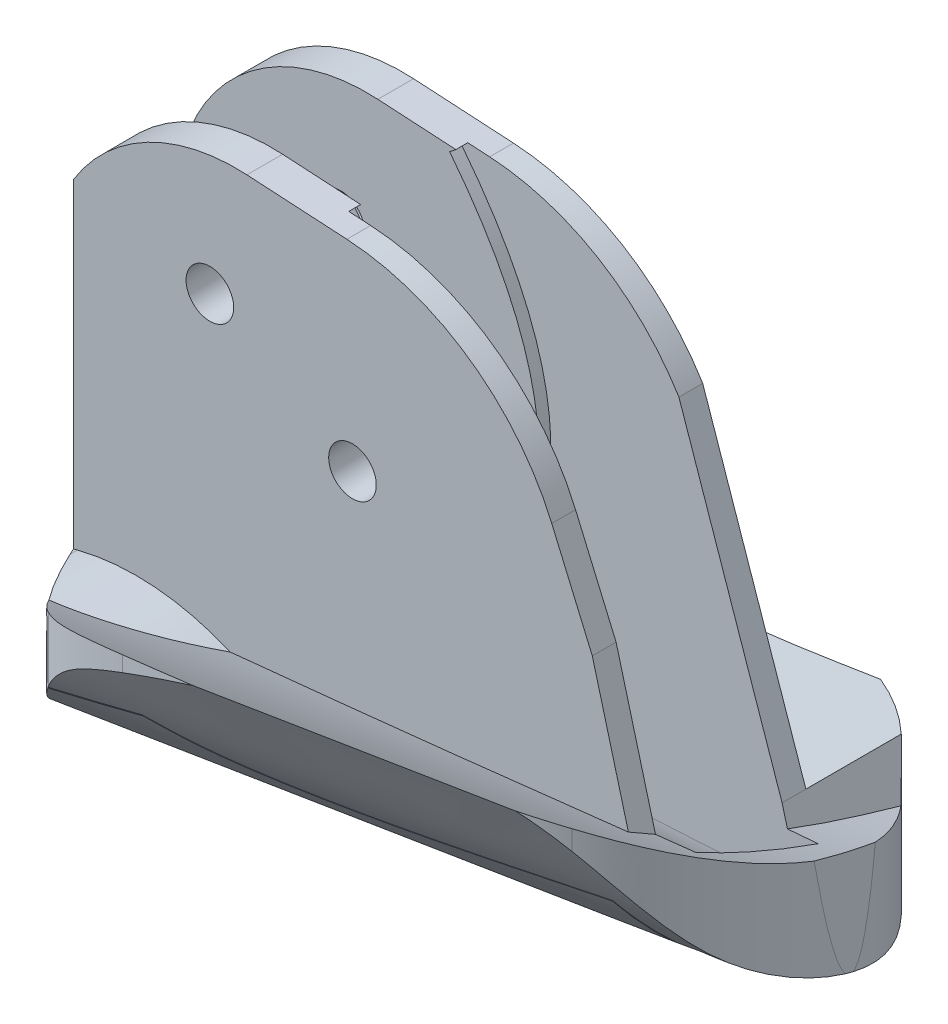
SolidWorks part; units mm, degrees
ref_plane "Спереди" through (0, 0, 0) normal (0, 0, 1) x (1, 0, 0)
ref_plane "Сверху" through (0, 0, 0) normal (0, 1, 0) x (1, 0, 0)
ref_plane "Справа" through (0, 0, 0) normal (1, 0, 0) x (0, 0, -1)
sketch "Sketch5" plane through (0, 0, 0) normal (0, 0, 1) x (1, 0, 0)
  line L0 (1.7523, 0.4742) -> (37.3029, 86.8114) construction
  line L1 (-1.0106, -0.6044) -> (29.6618, 87.5839) construction
  line L2 (0, 0) -> (17.8901, 43.1295)
  line L3 (0, 0) -> (114.3643, 0) construction
  line L4 (23.8823, 39.6684) -> (24.5035, 51.2503)
  line B0 (17.4507, 115.16) -> (29.9551, 112.6983)
  spline B1 degree 3 poles (29.9551, 112.6983) (28.321, 116.0983) (27.9284, 121.1676) (30.1713, 134.4746) (29.8473, 132.0116) (30.6222, 139.9349) (27.0176, 140.9027) knots 0 0 0 0 0.297085 0.369784 0.687298 1 1 1 1
  spline B2 degree 2 poles (27.0176, 140.9027) (20.5603, 128.6427) (17.4507, 115.16) knots 0 0 0 1 1 1
  spline B3 degree 2 poles (27.0176, 140.9027) (26.5004, 134.6878) (22.2537, 130.5645) knots 0 0 0 1 1 1
  line B4 (17.1977, 114.3508) -> (29.842, 112.2111)
  line B5 (28.7001, 84.8969) -> (10.3668, 87.513)
  spline B6 degree 1 poles (17.1977, 114.3508) (10.3668, 87.513) knots 0 0 1 1
  spline B7 degree 2 poles (29.842, 112.2111) (22.5534, 98.8452) (28.7001, 84.8969) knots 0 0 0 1 1 1
  line B8 (10.1904, 87.4159) -> (28.2572, 84.4958)
  line B9 (32.8909, 45.7292) -> (10.0695, 42.8593)
  spline B10 degree 2 poles (10.1904, 87.4159) (10.0234, 65.1379) (10.0695, 42.8593) knots 0 0 0 1 1 1
  spline B11 degree 2 poles (28.2572, 84.4958) (20.6417, 64.1094) (32.8909, 45.7292) knots 0 0 0 1 1 1
  line B12 (10.2797, 36.8758) -> (3.9253, -13.9853)
  line B13 (3.9253, -13.9853) -> (33.9594, -31.0804)
  line B14 (33.9594, -31.0804) -> (45.9193, -27.7969)
  line B15 (45.9193, -27.7969) -> (58.2918, -13.9853)
  line B16 (58.2918, -13.9853) -> (69.0331, -4.9875)
  line B17 (69.0331, -4.9875) -> (82.514, 2.0236)
  line B18 (82.514, 2.0236) -> (89.2736, 3.8794)
  line B19 (89.2736, 3.8794) -> (92.4846, 9.5208)
  line B20 (92.4846, 9.5208) -> (96.8914, 17.263)
  line B21 (96.8914, 17.263) -> (101.4978, 21.1217)
  line B22 (101.4978, 21.1217) -> (103.9241, 23.1541)
  line B23 (104.261, 27.4157) -> (104.5375, 25.5318)
  line B24 (84.192, 21.2056) -> (87.7484, 22.7822)
  line B25 (87.7484, 22.7822) -> (92.912, 27.4956)
  line B26 (71.6086, 15.6268) -> (84.192, 21.2056)
  line B27 (92.912, 27.4956) -> (95.357, 29.7274)
  line B28 (95.357, 29.7274) -> (96.8049, 29.9399)
  line B29 (71.6086, 15.6268) -> (53.4239, 15.2713)
  line B30 (48.0904, 17.5622) -> (39.9394, 26.4919)
  line B31 (39.9394, 26.4919) -> (33.9594, 37.99)
  line B32 (33.9594, 37.99) -> (10.2797, 36.8758)
  line B33 (96.8049, 29.9399) -> (99.4078, 30.2175)
  line B34 (99.4078, 30.2175) -> (102.2786, 29.261)
  line B35 (102.2786, 29.261) -> (104.261, 27.4157)
  line B36 (104.5375, 25.5318) -> (103.9241, 23.1541)
  arc B37 (53.4239, 15.2713) -> (48.0904, 17.5622) centre (53.2864, 22.3051) cw
  spline B38 degree 3 poles (104.261, 27.4157) (103.5289, 27.0494) (99.8378, 26.2685) (94.8982, 17.2338) (98.6516, 18.7375) knots 0 0 0 0 0.441207 1 1 1 1
  line B39 (27.7375, 116.5129) -> (14.1959, 87.8955)
  line B40 (27.7375, 116.5129) -> (25.9485, 114.8372)
  line B41 (25.9485, 114.8372) -> (27.5763, 114.067)
  line B42 (27.7375, 116.5129) -> (27.5763, 114.067)
  line B43 (26.1527, 88.0864) -> (17.8901, 43.1295)
  line B44 (19.3622, 85.005) -> (23.8823, 39.6684)
  line B45 (19.3622, 85.005) -> (17.7584, 73.9508)
  line B46 (17.7584, 73.9508) -> (23.117, 74.485)
  line B47 (23.117, 74.485) -> (19.3622, 85.005)
  line B48 (26.1527, 88.0864) -> (23.7481, 82.7635)
  line B49 (23.7481, 82.7635) -> (25.1278, 82.5099)
  line B50 (25.1278, 82.5099) -> (26.5087, 82.2561)
  line B51 (26.5087, 82.2561) -> (26.1527, 88.0864)
  line B52 (26.1527, 88.0864) -> (19.3622, 85.005)
  line B53 (19.3622, 85.005) -> (22.3683, 87.7853)
  line B54 (22.3683, 87.7853) -> (22.9012, 86.6109)
  line B55 (22.9012, 86.6109) -> (23.4998, 85.2917)
  line B56 (23.4998, 85.2917) -> (19.3622, 85.005)
  dimension "D1" = 93.37
  dimension "D2" = 93.37
  dimension "D4" = 67.471
  dimension "D5" = 8.764
sketch_block_instance "Block1-1"
sketch_block "Block1"
sketch_block_instance "Block2-1"
sketch_block "Block2"
sketch_block_instance "Block3-1"
sketch_block "Block3"
sketch_block_instance "Block18-1"
sketch_block "Block18"
sketch_block_instance "Block44-1"
sketch_block "Block44"
sketch_block_instance "Block46-1"
sketch_block "Block46"
sketch_block_instance "Block47-1"
sketch_block "Block47"
sketch_block_instance "Block48-1"
sketch_block "Block48"
sketch_block_instance "Block50-1"
sketch_block "Block50"
sketch "Sketch10" plane through (0, 0, 0) normal (0, 0, 1) x (1, 0, 0)
  line L0 (29.8177, 47.6353) -> (33.9594, 37.99)
  line L1 (23.8823, 39.6684) -> (24.3862, 39.4642) construction
  line L2 (23.8823, 39.6684) -> (24.2846, 40.0707) construction
  line L3 (33.9594, 37.99) -> (36.9938, 26.6828)
  line L21 (10.2797, 36.8758) -> (12.7888, 23.6588)
  line L22 (12.7888, 23.6588) -> (36.9938, 26.6828)
  line L23 (10.2797, 36.8758) -> (12.3212, 48.6513)
  line L24 (12.3212, 48.6513) -> (29.8177, 47.6353)
  circle A0 centre (17.8901, 43.1295) radius 1
  circle A1 centre (23.8823, 39.6684) radius 1
  dimension "D1" = 2
  dimension "D2" = 2
extrude "Boss-Extrude5" add sketch "Sketch10" along normal mid plane 15
sketch "Sketch11" plane through (0, 0, 7.5) normal (0, 0, 1) x (1, 0, 0)
  line L0 (17.8254, 32.4239) -> (9.1237, 30.2079)
  line L1 (37.7529, 30.846) -> (34.6935, 60.2717)
  line L2 (34.6935, 60.2717) -> (6.5943, 53.1599)
  line L3 (6.5943, 53.1599) -> (9.1237, 30.2079)
  line L4 (37.7529, 30.846) -> (30.6791, 30.1551) construction
  line L5 (30.6791, 30.1551) -> (19.269, 26.7342) construction
  line L6 (19.269, 26.7342) -> (17.8254, 32.4239) construction
  line L7 (12.3212, 48.6513) -> (10.2797, 36.8758) construction
  spline S1 degree 3 poles (37.7529, 30.846) (30.6791, 30.1551) (19.269, 26.7342) (17.8254, 32.4239) knots 0 0 0 0 1 1 1 1
extrude "Cut-Extrude1" cut sketch "Sketch11" against normal blind 4
fillet "Fillet1" radius 10 1 edges at (29.8177, 47.6353, -2)
extrude "Cut-Extrude6" cut sketch "Sketch11<2>" against normal blind 10 from offset 11 offset against normal yes
sketch "Sketch11<2>" plane through (0, 0, 7.5) normal (0, 0, 1) x (1, 0, 0) same geometry as "Sketch11"
sketch "Sketch16" plane through (0, 0, 0) normal (0, 0, 1) x (1, 0, 0)
  line L1 (10.0743, 54.3608) -> (34.4186, 54.3608)
  line L2 (10.0743, 54.3608) -> (10.0743, 40.6451)
  line L3 (10.0743, 40.6451) -> (34.4186, 36.6644)
  line L4 (34.4186, 54.3608) -> (34.4186, 36.6644)
extrude "Cut-Extrude7" cut sketch "Sketch16" against normal mid plane 4
sketch "Sketch26" plane through (41.1882, 11.0532, 0) normal (0.9658, 0.2592, 0) x (0, 0, -1)
  line L12 (2, 27.8898) -> (2, 26.5356)
  line L13 (2, 26.5356) -> (-2, 26.5356)
  line L14 (-2, 26.5356) -> (-2, 27.8898)
  line L15 (-2, 27.8898) -> (-3.5, 27.8898)
  line L16 (-3.5, 27.8898) -> (-3.5, 20.2671)
  line L17 (-3.5, 20.2671) -> (-7.5, 20.2671)
  line L18 (-7.5, 20.2671) -> (-7.5, 16.1826)
  line L19 (-7.5, 16.1826) -> (7.5, 16.1826)
  line L20 (7.5, 16.1826) -> (7.5, 20.2671)
  line L21 (7.5, 20.2671) -> (3.5, 20.2671)
  line L22 (3.5, 20.2671) -> (3.5, 27.8898)
  line L23 (3.5, 27.8898) -> (2, 27.8898)
  line L24 (2, 27.8898) -> (2, 26.5356)
  line L25 (2, 26.5356) -> (-2, 26.5356)
  line L26 (-2, 26.5356) -> (-2, 27.8898)
  line L27 (-2, 27.8898) -> (-3.5, 27.8898)
  line L28 (-3.5, 27.8898) -> (-3.5, 20.2671)
  line L29 (-3.5, 20.2671) -> (-7.5, 20.2671)
  line L30 (-7.5, 20.2671) -> (-7.5, 16.1826)
  line L31 (-7.5, 16.1826) -> (7.5, 16.1826)
  line L32 (7.5, 16.1826) -> (7.5, 20.2671)
  line L33 (7.5, 20.2671) -> (3.5, 20.2671)
  line L34 (3.5, 20.2671) -> (3.5, 27.8898)
  line L35 (3.5, 27.8898) -> (2, 27.8898)
  dimension "D1" = 0
extrude "Boss-Extrude11" add sketch "Sketch26" along normal blind 9
sketch "Sketch28" plane through (-4.1944, 15.6296, 0) normal (0.2592, -0.9658, 0) x (0.9658, 0.2592, 0)
  line L0 (38.2441, 4.6151) -> (38.2441, -4.6151) construction
  line L1 (51.6455, 0) -> (42.6455, 0) construction
  line L2 (51.6455, 7.5) -> (51.6455, -7.5) construction
  line L3 (42.6455, 7.5) -> (42.6455, -7.5) construction
  circle A0 centre (38.2441, 4.6151) radius 1
  circle A1 centre (38.2441, -4.6151) radius 1
  point P10 (38.2441, 0)
  dimension "D1" = 2
sketch "Sketch32" plane through (49.8806, 13.3859, 0) normal (0.9658, 0.2592, 0) x (0, 0, -1)
  line L12 (3.5, 27.8898) -> (2, 27.8898)
  line L13 (2, 27.8898) -> (2, 26.5356)
  line L14 (2, 26.5356) -> (-2, 26.5356)
  line L15 (-2, 26.5356) -> (-2, 27.8898)
  line L16 (-2, 27.8898) -> (-3.5, 27.8898)
  line L17 (-3.5, 27.8898) -> (-3.5, 20.2671)
  line L18 (-3.5, 20.2671) -> (-7.5, 20.2671)
  line L19 (-7.5, 20.2671) -> (-7.5, 16.1826)
  line L20 (-7.5, 16.1826) -> (7.5, 16.1826)
  line L21 (7.5, 16.1826) -> (7.5, 20.2671)
  line L22 (7.5, 20.2671) -> (3.5, 20.2671)
  line L23 (3.5, 20.2671) -> (3.5, 27.8898)
  line L24 (3.5, 27.8898) -> (2, 27.8898)
  line L25 (2, 27.8898) -> (2, 26.5356)
  line L26 (2, 26.5356) -> (-2, 26.5356)
  line L27 (-2, 26.5356) -> (-2, 27.8898)
  line L28 (-2, 27.8898) -> (-3.5, 27.8898)
  line L29 (-3.5, 27.8898) -> (-3.5, 20.2671)
  line L30 (-3.5, 20.2671) -> (-7.5, 20.2671)
  line L31 (-7.5, 20.2671) -> (-7.5, 16.1826)
  line L32 (-7.5, 16.1826) -> (7.5, 16.1826)
  line L33 (7.5, 16.1826) -> (7.5, 20.2671)
  line L34 (7.5, 20.2671) -> (3.5, 20.2671)
  line L35 (3.5, 20.2671) -> (3.5, 27.8898)
  dimension "D1" = 0
extrude "Cut-Extrude9" cut sketch "Sketch32" against normal blind 9
fillet "Fillet2" radius 8 2 edges at (12.3212, 48.6513, 2.75) (12.3212, 48.6513, -2.75)
fillet "Fillet3" radius 10 2 edges at (17.8254, 32.4239, 5.5) (17.8254, 32.4239, -5.5)
sketch "Sketch33" plane through (0, 0, -7.5) normal (0, 0, -1) x (-1, 0, 0)
  line L8 (-11.4338, 30.7962) -> (-12.3264, 31.0236)
  line L9 (-35.9352, 30.6278) -> (-36.9938, 26.6828)
  line L10 (-36.9938, 26.6828) -> (-12.7888, 23.6588)
  line L15 (-12.7888, 23.6588) -> (-11.4338, 30.7962)
  line L16 (-11.4338, 30.7962) -> (-12.3264, 31.0236)
  line L17 (-35.9352, 30.6278) -> (-36.9938, 26.6828)
  line L18 (-36.9938, 26.6828) -> (-12.7888, 23.6588)
  line L23 (-12.7888, 23.6588) -> (-11.4338, 30.7962)
  arc A1 (-12.3264, 31.0236) -> (-19.6523, 30.0735) centre (-14.7943, 21.3329) ccw
  arc A2 (-12.3264, 31.0236) -> (-19.6523, 30.0735) centre (-14.7943, 21.3329) ccw
  spline S1 degree 3 poles (-2248.4451, 2036.9138) (2398.2149, -1976.4492) (-2488.6024, 2006.9679) (2269.0143, -1889.1309) knots -4.784802 -4.784802 -4.784802 -4.784802 6.242241 6.242241 6.242241 6.242241 only from (-19.6523, 30.0735) to (-35.9352, 30.6278)
  spline S2 degree 3 poles (-19.6523, 30.0735) (-23.0941, 28.1606) (-30.3498, 29.8586) (-35.9352, 30.6278) knots 0.191602 0.191602 0.191602 0.191602 0.918086 0.918086 0.918086 0.918086
  line M11 (-11.4338, 30.7962) -> (-12.3264, 31.0236)
  arc M12 (-12.3264, 31.0236) -> (-19.6523, 30.0735) centre (-14.7943, 21.3329) ccw
  spline M13 degree 3 poles (-37.7529, 30.846) (-30.6791, 30.1551) (-19.269, 26.7342) (-17.8254, 32.4239) knots 0 0 0 0 1 1 1 1 only from (-19.6523, 30.0735) to (-35.9352, 30.6278)
  line M14 (-35.9352, 30.6278) -> (-36.9938, 26.6828)
  line M15 (-36.9938, 26.6828) -> (-12.7888, 23.6588)
  line M19 (-36.9938, 26.6828) -> (-12.7888, 23.6588)
  line M20 (-12.7888, 23.6588) -> (-11.4338, 30.7962)
  dimension "D1" = 0
extrude "Boss-Extrude15" add sketch "Sketch33" along normal blind 2 contours M20 M11 M12 M13 M14 M15 M19 region at (22.5887, 27.6255, -7.5)
ref_plane "Plane1" through (38.4615, 25.5911, -2.6463) normal (-0.987, -0.0285, 0.1584) x (0.1583, 0.0046, 0.9874)
sketch "Sketch34" plane through (38.4615, 25.5911, -2.6463) normal (-0.987, -0.0285, 0.1584) x (0.1583, 0.0046, 0.9874)
  line L1 (-9.9613, -0.7387) -> (-10.5398, -8.5297)
  line L3 (-10.5398, -8.5297) -> (14.0671, -4.6342)
  line L4 (14.0671, -4.6342) -> (11.4688, 6.9569)
  line L5 (11.4688, 6.9569) -> (11.2103, 7.3048)
  line L6 (9.3619, 9.0979) -> (11.2103, 7.3048)
  spline S1 degree 3 poles (9.3619, 9.0979) (8.0808, 7.1287) (6.1822, 3.4329) (1.2126, 0.2397) (-4.0234, -1.2627) (-7.9896, -1.4142) (-9.9613, -0.7387) knots 0 0 0 0 0.305307 0.51081 0.734727 1 1 1 1
extrude "Cut-Extrude10" cut sketch "Sketch34" along normal blind 39
sketch "Sketch35" plane through (38.4615, 25.5911, -2.6463) normal (-0.987, -0.0285, 0.1584) x (0.1583, 0.0046, 0.9874)
  line L0 (9.4005, 9.1848) -> (3.3279, 5.0721) construction
  line L1 (3.3279, 5.0721) -> (-2.7348, 1.7749) construction
  line L2 (-2.7348, 1.7749) -> (-13.1414, 3.4012) construction
  line L5 (-13.1414, 3.4012) -> (-9.5787, -0.8831) construction
  spline S0 degree 3 poles (9.4005, 9.1848) (8.0149, 7.019) (5.8425, 2.8785) (-1.139, -0.8866) (-6.3054, -1.5967) (-9.5787, -0.8831) knots 0 0 0 0 0.341444 0.573298 1 1 1 1
  spline S1 degree 3 poles (6.8156, 5.1075) (6.3414, 4.4434) (5.0935, 2.8969) (3.4618, 1.7144) (2.4324, 1.1336) knots 0.201432 0.201432 0.201432 0.201432 0.305307 0.455135 0.455135 0.455135 0.455135 construction
  spline S2 degree 3 poles (-5.3799, -1.1913) (-4.8408, -1.1453) (-2.5388, -0.8367) (0.0833, -0.0843) (2.0499, 0.9178) (2.4324, 1.1336) knots 0.196975 0.196975 0.196975 0.196975 0.265273 0.48919 0.544865 0.544865 0.544865 0.544865 construction
  spline S3 degree 4 poles (9.4005, 9.1848) (3.3279, 5.0721) (-2.7348, 1.7749) (-13.1414, 3.4012) (-9.5787, -0.8831) knots 0 0 0 0 0 1 1 1 1 1
extrude "Boss-Extrude16" add sketch "Sketch35" along normal blind 35
sketch "Sketch36" plane through (0, 0, 0) normal (0, 1, 0) x (1, 0, 0)
  line L0 (22.2747, 9.702) -> (19.2802, 8.5421)
  circle A0 centre (26.2258, -0.6503) radius 26.4347
  arc A1 (32.0453, -8.6033) -> (26.2258, -9.3573) centre (2192.8185, -16707.6767) ccw
  spline S27 degree 3 poles (27.8922, 10.6475) (26.9334, 10.6337) (25.9886, 10.5289) (24.5845, 10.2862) (24.1189, 10.1901) (23.1921, 9.9682) (22.73, 9.842) (22.2747, 9.702) knots 0 0 0 0 0.5 0.5 0.75 0.75 1 1 1 1
  spline S29 degree 3 poles (19.2802, 8.5421) (18.1759, 8.0221) (17.1049, 7.4097) (15.0752, 6.0455) (14.1101, 5.2944) (13.1983, 4.4671) knots 0 0 0 0 0.5 0.5 1 1 1 1
  spline S30 degree 3 poles (13.1983, 4.4671) (12.8563, 4.1568) (12.5211, 3.838) (12.0629, 3.3185) (11.9182, 3.1375) (11.6617, 2.757) (11.5505, 2.5565) (11.4557, 2.346) knots 0 0 0 0 0.5 0.5 0.75 0.75 1 1 1 1
  spline S31 degree 3 poles (11.4557, 2.346) (11.284, 1.9646) (11.1649, 1.5649) (11.0081, 0.7554) (10.9712, 0.3454) (10.9879, -0.0592) knots 0 0 0 0 0.5 0.5 1 1 1 1
  spline S32 degree 3 poles (10.9879, -0.0592) (10.9979, -0.3025) (11.0294, -0.5425) (11.1263, -1.0087) (11.1909, -1.2366) (11.4103, -1.9049) (11.5882, -2.33) (11.7801, -2.7383) knots 0 0 0 0 0.25 0.25 0.5 0.5 1 1 1 1
  spline S33 degree 3 poles (11.7801, -2.7383) (11.9136, -3.0221) (12.0539, -3.2973) (12.1957, -3.5663) knots 0 0 0 0 1 1 1 1
  spline S34 degree 3 poles (12.1957, -3.5663) (12.4115, -3.9755) (12.6305, -4.3688) (13.0779, -5.1243) (13.3054, -5.4845) (13.7845, -6.1648) (14.0386, -6.4847) (14.5871, -7.0709) (14.8803, -7.3391) (15.1896, -7.5863) knots 0 0 0 0 0.25 0.25 0.5 0.5 0.75 0.75 1 1 1 1
  spline S35 degree 3 poles (15.1896, -7.5863) (15.4845, -7.8221) (15.7909, -8.0364) (16.4511, -8.4118) (16.8052, -8.5727) (17.6001, -8.8248) (18.0301, -8.9109) (18.9251, -9.0401) (19.3853, -9.0839) (19.8478, -9.1216) knots 0 0 0 0 0.25 0.25 0.5 0.5 0.75 0.75 1 1 1 1
  spline S36 degree 3 poles (19.8478, -9.1216) (20.3759, -9.1646) (20.9057, -9.2003) (21.9634, -9.2645) (22.4923, -9.2916) (24.0799, -9.3576) (25.1387, -9.3807) (26.2258, -9.3573) knots 0 0 0 0 0.25 0.25 0.5 0.5 1 1 1 1
  spline S37 degree 3 poles (32.0453, -8.6033) (32.4849, -8.4754) (32.895, -8.3314) (33.6607, -8.0097) (34.0089, -7.8361) (34.332, -7.6481) knots 0 0 0 0 0.5 0.5 1 1 1 1
  spline S38 degree 3 poles (34.332, -7.6481) (34.9868, -7.2672) (35.5151, -6.84) (35.9629, -6.3477) knots 0 0 0 0 1 1 1 1
  spline S39 degree 3 poles (35.9629, -6.3477) (36.2177, -6.0676) (36.4446, -5.7715) (36.8644, -5.1443) (37.0562, -4.8132) (37.4091, -4.1124) (37.5701, -3.7428) (37.8622, -2.9604) (37.9936, -2.5457) (38.2178, -1.6879) (38.3115, -1.2432) (38.457, -0.321) (38.5089, 0.1566) (38.5454, 0.8995) (38.5505, 1.1526) (38.5441, 1.661) (38.5326, 1.9167) (38.4691, 2.6875) (38.3891, 3.2062) (38.185, 3.9872) (38.1026, 4.2476) (37.9091, 4.7535) (37.7978, 5.0008) (37.5471, 5.4841) (37.4078, 5.7202) (37.102, 6.1813) (36.9347, 6.4071) (36.4059, 7.0544) (36.0151, 7.4506) (35.1713, 8.185) (34.7172, 8.5233) (33.7779, 9.1303) (33.2898, 9.4021) (32.5283, 9.7588) (32.2684, 9.8696) (31.743, 10.0689) (31.4778, 10.1573) (30.6747, 10.3882) (30.1294, 10.4966) (29.0203, 10.6303) (28.4554, 10.6556) (27.8922, 10.6475) knots 0 0 0 0 0.0625 0.0625 0.125 0.125 0.1875 0.1875 0.25 0.25 0.3125 0.3125 0.375 0.375 0.40625 0.40625 0.4375 0.4375 0.5 0.5 0.53125 0.53125 0.5625 0.5625 0.59375 0.59375 0.625 0.625 0.6875 0.6875 0.75 0.75 0.8125 0.8125 0.84375 0.84375 0.875 0.875 0.9375 0.9375 1 1 1 1
extrude "Cut-Extrude11" cut sketch "Sketch36" along normal blind 50
sketch "Sketch37" plane through (0, 0, 0) normal (0, 1, 0) x (1, 0, 0)
  circle A0 centre (31.6606, 4.5) radius 1
  circle A1 centre (31.6606, -4.5) radius 1
  dimension "D1" = 2
sketch "Sketch38" plane through (0, 0, 0) normal (0, 0, 1) x (1, 0, 0)
  line L0 (25.6305, 35.1974) -> (28.424, 17.492)
  line L1 (28.424, 17.492) -> (38.6586, 12.2021)
  line L2 (38.6586, 12.2021) -> (36.1416, 49.0283)
  line L3 (36.1416, 49.0283) -> (23.9734, 49.0283)
  line L4 (22.4652, 47.8412) -> (27.7083, 41.1798) construction
  line L5 (27.7083, 41.1798) -> (25.6305, 35.1974) construction
  line L6 (23.9734, 49.0283) -> (22.4652, 47.8412)
  spline S0 degree 2 poles (22.4652, 47.8412) (27.7083, 41.1798) (25.6305, 35.1974) knots 0 0 0 1 1 1
extrude "Cut-Extrude13" cut sketch "Sketch38" against normal mid plane 5
fillet "Fillet5" radius 3 1 edges
sketch "Sketch39" plane through (0, 0, -3.5) normal (0, 0, -1) x (-1, 0, 0)
  line L0 (-31.1496, 44.5336) -> (-35.9352, 30.6278)
  line L1 (-32.2564, 41.9561) -> (-33.9594, 37.99) construction
  line L2 (-35.9352, 30.6278) -> (-33.9594, 37.99)
  line L3 (-33.9594, 37.99) -> (-31.1496, 44.5336)
extrude "Cut-Extrude14" cut sketch "Sketch39" against normal blind 2
sketch "Sketch40" plane through (0, 0, 2.5) normal (0, 0, -1) x (-1, 0, 0)
  line L0 (-28.8475, 43.6873) -> (-28.2997, 34.3422)
  line L2 (-28.8475, 43.6873) -> (-33.9594, 37.99)
  line L3 (-33.9594, 37.99) -> (-34.7872, 34.9054)
  line L4 (-33.9594, 37.99) -> (-35.615, 31.8208) construction
  line L6 (-35.615, 31.8208) -> (-28.2997, 34.3422)
  line L7 (-34.7872, 34.9054) -> (-35.615, 31.8208)
ref_plane "Plane2" through (12.6094, 32.8322, 0) normal (0.3585, 0.9335, 0) x (0.9335, -0.3585, 0)
sketch "Sketch41" plane through (12.6094, 32.8322, 0) normal (0.3585, 0.9335, 0) x (0.9335, -0.3585, 0)
  line L0 (5.5568, 4.75) -> (10.5568, 4.75) construction
  line L3 (5.5568, 6) -> (10.5568, 6)
  line L4 (5.5568, 6) -> (5.5568, 2.75) construction
  line L9 (5.5568, 3.5) -> (10.5568, 3.5)
  arc A2 (4.3068, 4.75) -> (5.5568, 3.5) centre (5.5568, 4.75) ccw
  arc A3 (10.5568, 3.5) -> (11.8068, 4.75) centre (10.5568, 4.75) ccw
  arc A4 (5.5568, 6) -> (4.3068, 4.75) centre (5.5568, 4.75) ccw
  arc A5 (11.8068, 4.75) -> (10.5568, 6) centre (10.5568, 4.75) ccw
  point P3 (8.0568, 4.75)
  dimension "D1" = 5
extrude "Cut-Extrude15" cut sketch "Sketch41" against normal blind 10 and the other way blind 10
